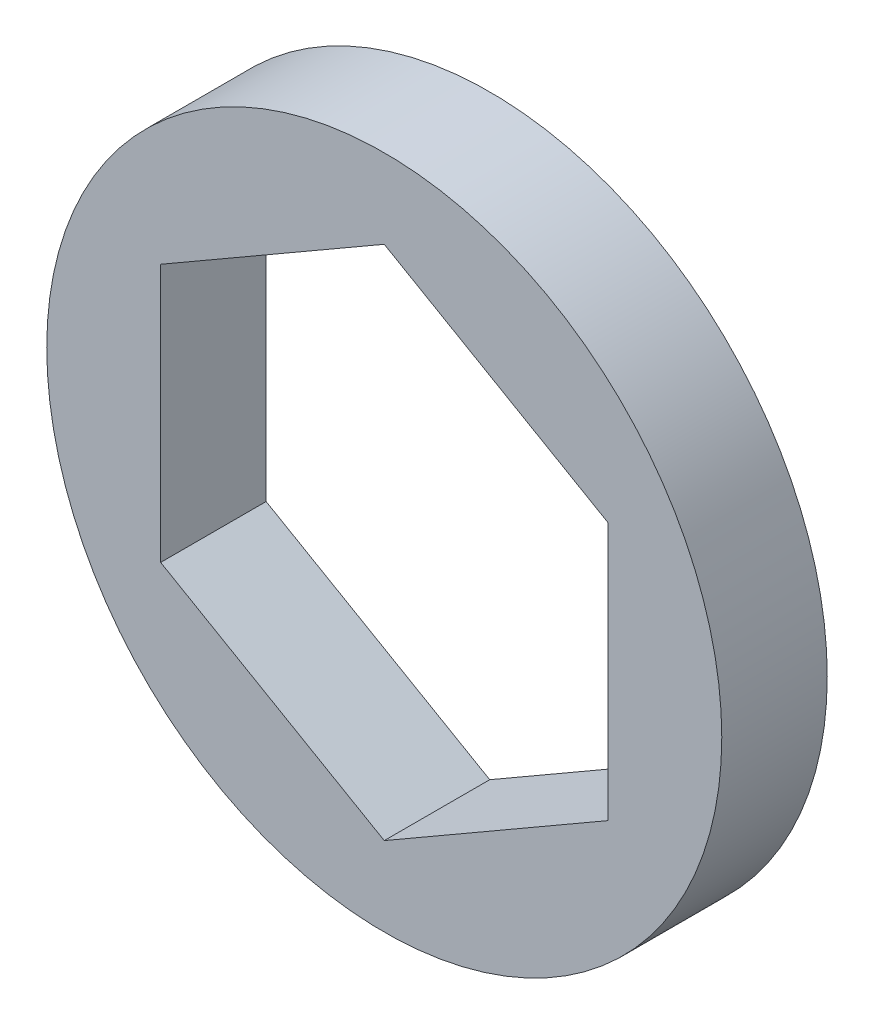
SolidWorks part; units mm, degrees
material "Nylon 101"
ref_plane "Front Plane" through (0, 0, 0) normal (0, 0, 1) x (1, 0, 0)
ref_plane "Top Plane" through (0, 0, 0) normal (0, 1, 0) x (1, 0, 0)
ref_plane "Right Plane" through (0, 0, 0) normal (1, 0, 0) x (0, 0, -1)
sketch "Sketch1" plane through (0, 0, 0) normal (0, 0, 1) x (1, 0, 0)
  line L1 (0, 7.7723) -> (-6.731, 3.8861)
  line L2 (-6.731, 3.8861) -> (-6.731, -3.8861)
  line L3 (-6.731, -3.8861) -> (0, -7.7723)
  line L4 (0, -7.7723) -> (6.731, -3.8861)
  line L5 (6.731, -3.8861) -> (6.731, 3.8861)
  line L6 (6.731, 3.8861) -> (0, 7.7723)
  circle A0 centre (0, 0) radius 10.16
  circle A1 centre (0, 0) radius 6.731 construction
  dimension "D1" = 20.32
  dimension "D2" = 13.462
extrude "Boss-Extrude1" add sketch "Sketch1" along normal mid plane 3.175
